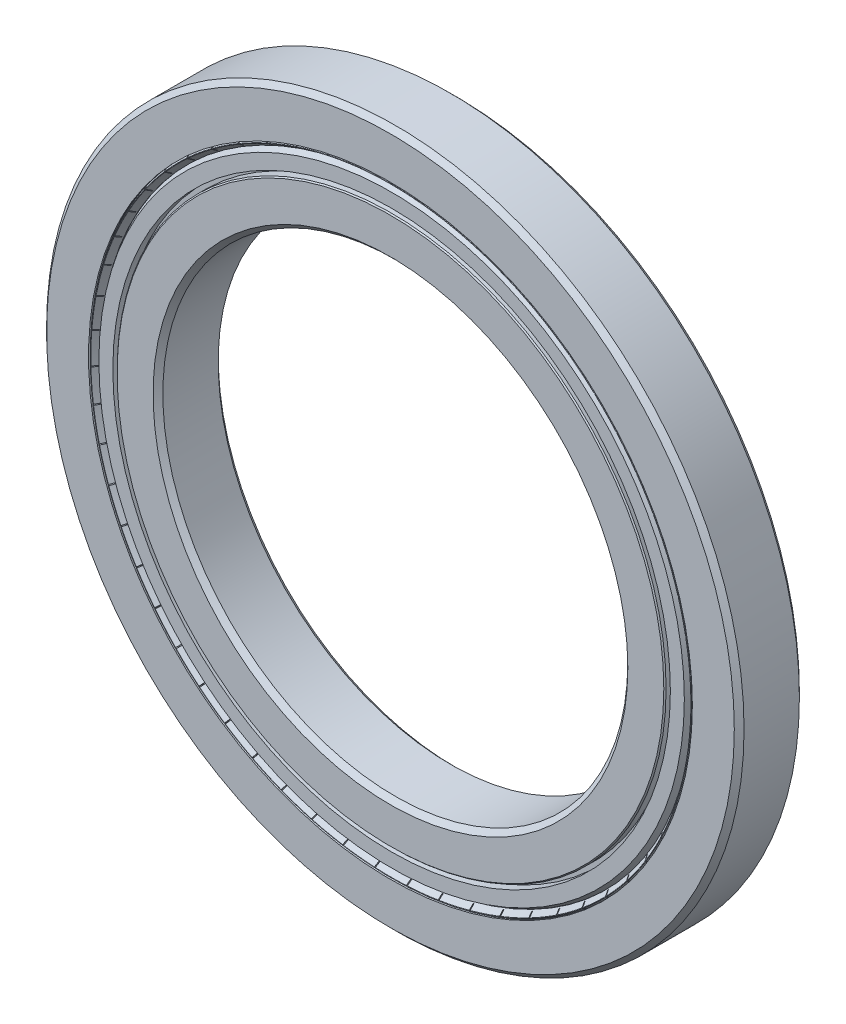
SolidWorks part; units mm, degrees
ref_plane "Front Plane" through (0, 0, 0) normal (0, 0, 1) x (1, 0, 0)
ref_plane "Top Plane" through (0, 0, 0) normal (0, 1, 0) x (1, 0, 0)
ref_plane "Right Plane" through (0, 0, 0) normal (1, 0, 0) x (0, 0, -1)
sketch "Sketch1" plane through (0, 0, 0) normal (0, 0, 1) x (1, 0, 0)
  circle A0 centre (0, 0) radius 25
  circle A1 centre (0, 0) radius 37.5
  dimension "OD" = 75
  dimension "ID" = 50
sketch "Sketch2" plane through (0, 0, 0) normal (1, 0, 0) x (0, 0, -1)
  line L0 (-3.5, 37.5) -> (3.5, 37.5)
  line L1 (-3.5, 25) -> (-3.5, -25) construction
  line L2 (3.5, 40) -> (3.5, -40) construction
  line L3 (-3.5, 0) -> (3.5, 0) construction
  line L6 (0, 37.5) -> (0, 25) construction
  circle A0 centre (0, 31.25) radius 2 construction
  point P8 (0, 37.5)
  dimension "Approx. Ball Dia." = 4
  dimension "Width" = 7
  dimension "For Shaft Diameter" = 50
  dimension "For Housing ID" = 80
sketch "Sketch3" plane through (0, 0, 0) normal (1, 0, 0) x (0, 0, -1)
  line L0 (0, 0) -> (0, 50) construction
  line L1 (-3.5, 25) -> (-3.5, -25) construction
  line L2 (2.975, 37.5) -> (-2.975, 37.5)
  line L3 (-2.975, 37.5) -> (-3.5, 36.975)
  line L4 (-3.5, 36.975) -> (-3.5, 32.4666)
  line L5 (-3.5, 32.4666) -> (-3.325, 32.4666)
  line L6 (-3.325, 32.4666) -> (-3.325, 32.8583)
  line L7 (-3.325, 32.8583) -> (-3.2013, 32.9821)
  line L8 (-3.2013, 32.9821) -> (-1, 32.9821)
  line L10 (-3.5, 37.5) -> (3.5, 37.5) construction
  line L12 (-3.325, 32.8583) -> (-3.325, 33.25) construction
  line L13 (3.2013, 32.9821) -> (1, 32.9821)
  line L14 (3.325, 32.8583) -> (3.2013, 32.9821)
  line L15 (3.325, 32.4666) -> (3.325, 32.8583)
  line L16 (3.5, 32.4666) -> (3.325, 32.4666)
  line L17 (3.5, 36.975) -> (3.5, 32.4666)
  line L18 (2.975, 37.5) -> (3.5, 36.975)
  line L19 (2.975, 25) -> (-2.975, 25)
  line L20 (-2.975, 25) -> (-3.5, 25.525)
  line L21 (-3.5, 25.525) -> (-3.5, 29.3942)
  line L22 (-3.5, 29.3942) -> (-3.3763, 29.5179)
  line L23 (-3.3763, 29.5179) -> (-1, 29.5179)
  line L25 (3.3763, 29.5179) -> (1, 29.5179)
  line L26 (3.5, 29.3942) -> (3.3763, 29.5179)
  line L27 (3.5, 25.525) -> (3.5, 29.3942)
  line L28 (2.975, 25) -> (3.5, 25.525)
  circle A2 centre (0, 31.25) radius 2 construction
  arc A3 (-1, 32.9821) -> (1, 32.9821) centre (0, 31.25) cw
  arc A4 (-1, 29.5179) -> (1, 29.5179) centre (0, 31.25) ccw
  point P5 (0, 33.25)
  point P31 (0, 37.5)
  point P37 (0, 25)
  dimension "D1" = 45
  dimension "D2" = 0.175
  dimension "D3" = 2
  dimension "D4" = 0.525
revolve "Revolve1" add sketch "Sketch3" angle 360 about L3
sketch "Sketch4" plane through (0, 0, 0) normal (1, 0, 0) x (0, 0, -1)
  line L0 (0, 33.25) -> (0, 29.25)
  line L1 (0, 37.5) -> (0, 25) construction
  circle A0 centre (0, 31.25) radius 2 construction
  arc A1 (0, 29.25) -> (0, 33.25) centre (0, 31.25) cw
revolve "Revolve2" add sketch "Sketch4" angle 360 about L6
pattern_circular "CirPattern1" count 29 over 360 about axis through (0, 0, 3.5) along (0, 0, -1) of bodies 106
sketch "Sketch5" plane through (0, 0, 0) normal (1, 0, 0) x (0, 0, -1)
  line L0 (-2, 31.25) -> (-2, 29.5179) construction
  line L1 (-3.3763, 29.5179) -> (-1, 29.5179) construction
  line L3 (-2, 29.5179) -> (-2.4588, 29.5179)
  line L4 (-2.4588, 29.5179) -> (-2.4588, 29.9767)
  line L5 (-2.4588, 29.9767) -> (-3.3763, 29.9767)
  line L6 (-3.3763, 29.9767) -> (-3.3763, 31.4781)
  line L7 (-3.3763, 31.4781) -> (-2.4588, 32.0079)
  line L8 (-2.4588, 32.0079) -> (-2, 32.0079)
  line L9 (-2, 32.0079) -> (-2, 29.5179)
  line L10 (0, 31.25) -> (0, 37.5) construction
  line L11 (2.4588, 32.0079) -> (2, 32.0079)
  line L12 (3.3763, 31.4781) -> (2.4588, 32.0079)
  line L13 (3.3763, 29.9767) -> (3.3763, 31.4781)
  line L14 (2.4588, 29.9767) -> (3.3763, 29.9767)
  line L15 (2.4588, 29.5179) -> (2.4588, 29.9767)
  line L16 (2, 29.5179) -> (2.4588, 29.5179)
  line L17 (2, 32.0079) -> (2, 29.5179)
  line L18 (-3.3763, 31.4781) -> (-2.9175, 31.4781) construction
  line L19 (-2.9175, 31.4781) -> (-2.4588, 31.4781) construction
  line L20 (-2.4588, 31.4781) -> (-2, 31.4781) construction
  line L21 (-2.4588, 32.0079) -> (-2.4588, 32.4666) construction
  circle A0 centre (0, 31.25) radius 2 construction
  dimension "D1" = 30
revolve "Revolve3" add sketch "Sketch5" angle 360 about L3
sketch "Sketch6" plane through (0, 0, 0) normal (1, 0, 0) x (0, 0, -1)
  line L0 (-2.7415, 32.4666) -> (-3.1937, 32.4666)
  line L1 (-3.1937, 32.4666) -> (-3.5, 32.2898)
  line L2 (-3.5, 32.2898) -> (-2.8465, 31.8322)
  line L4 (-3.3763, 31.4781) -> (-2.4588, 32.0079) construction
  line L5 (-2.7415, 31.8446) -> (-2.7415, 32.4666)
  line L6 (-3.5, 32.4666) -> (-3.325, 32.4666) construction
  line L7 (-2.8465, 31.8322) -> (-2.8115, 31.8322)
  line L8 (-2.8115, 31.8322) -> (-2.7415, 31.8446)
  line L9 (-3.5, 36.975) -> (-3.5, -36.975) construction
  line L11 (-2.8115, 31.8322) -> (-2.7765, 31.8322) construction
  line L12 (-2.7765, 31.8322) -> (-2.7415, 31.8322) construction
  point P27 (-2.9676, 32.4666)
  dimension "D1" = 30
  dimension "D3" = 10
  dimension "D2" = 35
  dimension "D4" = 0.035
  dimension "D5" = 0.3062
revolve "Revolve4" add sketch "Sketch6" angle 360 about L3
fillet "Fillet1" radius 0.035 1 edges at (32.2898, 0, 3.5)
sketch "Sketch7" plane through (0, 0, 0) normal (0, 0, 1) x (1, 0, 0)
  line L0 (-0.05, 32.4666) -> (-0.05, 32.5666)
  line L1 (-0.05, 32.4666) -> (0.05, 32.4666) construction
  line L2 (-0.05, 32.4666) -> (-0.05, 31.8322)
  line L3 (-0.05, 31.8322) -> (0.05, 31.8322) construction
  line L4 (0.05, 32.4666) -> (0.05, 31.8322)
  line L5 (-0.05, 32.5666) -> (0.05, 32.5666)
  line L6 (0.05, 32.5666) -> (0.05, 32.4666)
  line L7 (-0.05, 31.8322) -> (-0.05, 31.7322)
  line L8 (-0.05, 31.7322) -> (0.05, 31.7322)
  line L9 (0.05, 31.7322) -> (0.05, 31.8322)
  dimension "D1" = 0.1
extrude "Cut-Extrude1" cut sketch "Sketch7" along normal through all from vertex starting at point (0, 32.4666, 2.9676)
pattern_circular "CirPattern2" count 59 over 360 about axis through (0, 0, 3.5) along (0, 0, -1) of "Cut-Extrude1"
mirror "Mirror1" about plane through (0, 0, 0) normal (0, 0, 1) of bodies 120
equation "\"D2@Sketch3\"=\"Width@Sketch2\"*.025"
equation "\"D3@Sketch3\"=\"Approx. Ball Dia.@Sketch2\"*.5"
equation "\"D4@Sketch3\"=\"Width@Sketch2\"*.075"
equation "\"Approx No of Balls\"= ( pi * \"OD@Sketch1\" ) * .5 / \"Approx. Ball Dia.@Sketch2\""
equation "\"D1@CirPattern1\"=\"Approx No of Balls\""
equation "\"D4@Sketch6\"=\"D2@Sketch3\"*.2"
equation "\"D1@CirPattern2\"=\"Approx No of Balls\"*2"
equation "\"D5@Sketch6\"=\"D2@Sketch3\"*1.75"
equation "\"D1@Fillet1\"=\"d4@sketch6\""
